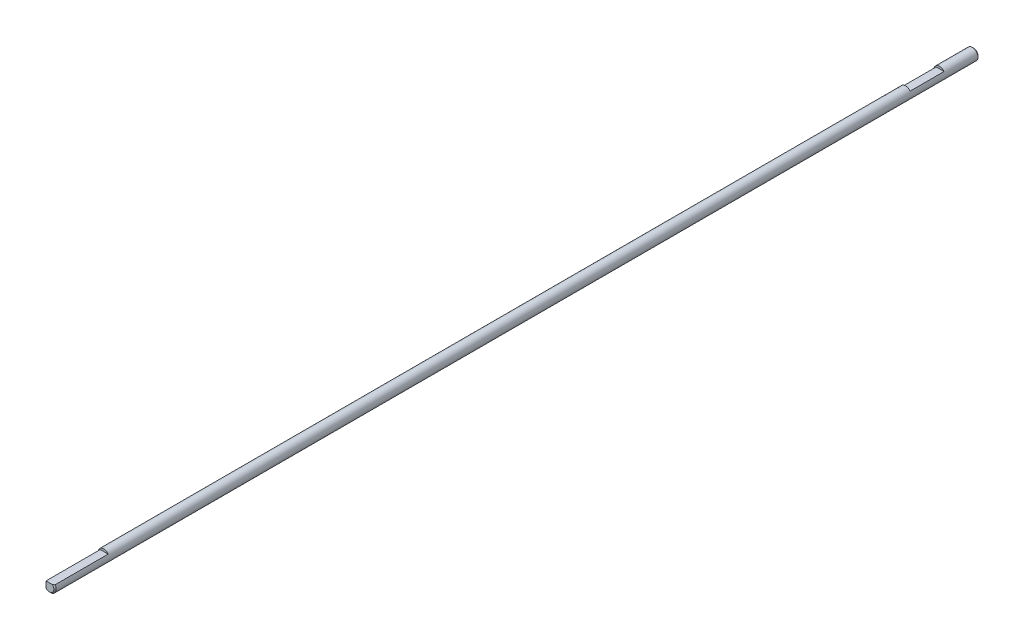
SolidWorks part; units mm, degrees
material "AISI 1020"
ref_plane "Спереди" through (0, 0, 0) normal (0, 0, 1) x (1, 0, 0)
ref_plane "Сверху" through (0, 0, 0) normal (0, 1, 0) x (1, 0, 0)
ref_plane "Справа" through (0, 0, 0) normal (1, 0, 0) x (0, 0, -1)
sketch "Эскиз1" plane through (0, 0, 0) normal (0, 0, 1) x (1, 0, 0)
  circle A0 centre (0, 0) radius 2.5
  dimension "D1" = 5
extrude "Body" add sketch "Эскиз1" along normal blind 408.5
chamfer "ChamferEdges" distance 0.5 angle 45 2 edges at (2.5, 0, 408.5) (2.5, 0, 0)
sketch "Sketch2" plane through (0, 0, 0) normal (1, 0, 0) x (0, 0, -1)
  line L0 (-408.5, 2) -> (-408.5, -2) construction
  line L1 (-30, 4.0099) -> (-15, 4.0099)
  line L2 (-30, 4.0099) -> (-30, 1.5)
  line L3 (-30, 1.5) -> (-15, 1.5)
  line L4 (-15, 4.0099) -> (-15, 1.5)
  line L6 (-408, -2.5) -> (-0.5, -2.5) construction
  line L11 (-384.5, 3.4421) -> (-384.5, 1.5)
  line L13 (-412.5, 3.4421) -> (-384.5, 3.4421)
  line L14 (-412.5, 3.4421) -> (-412.5, 1.5)
  line L15 (-412.5, 1.5) -> (-384.5, 1.5)
  point P8 (-36.7993, 9.6309)
  dimension "D1" = 30
  dimension "D2" = 4
  dimension "D3" = 15
  dimension "D4" = 24
extrude "FirstSlots" cut sketch "Sketch2" against normal through all both and the other way through all
pattern_circular "AnotherSlots" count 2 every 90 about axis through (0, 0, 408.5) along (0, 0, 1) of "FirstSlots"
